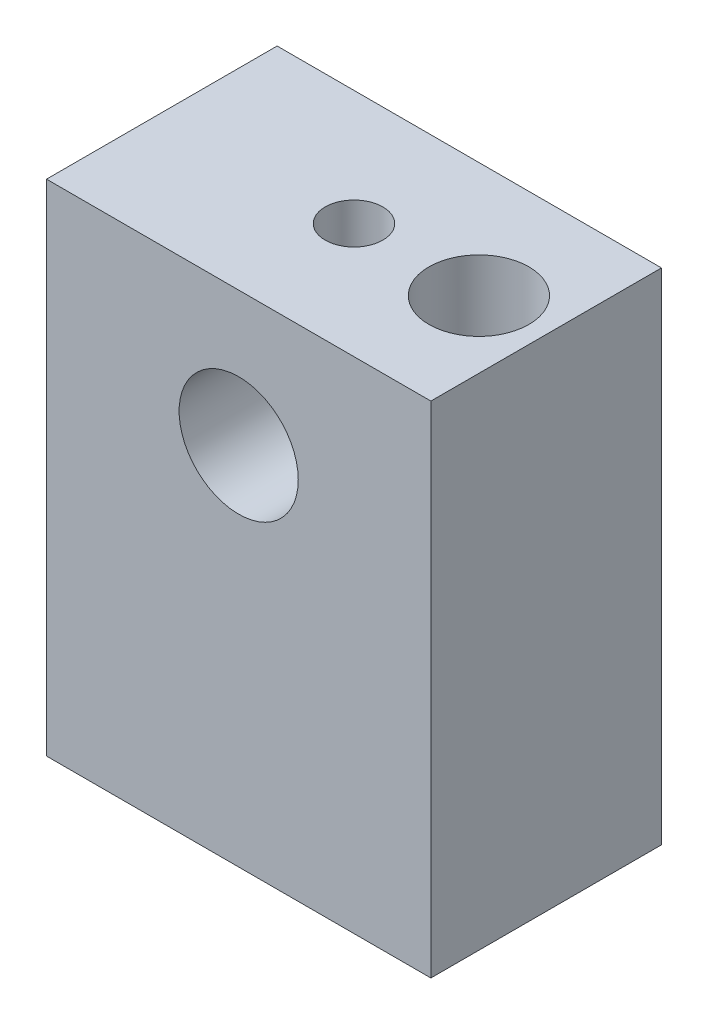
SolidWorks part; units mm, degrees
material "Brass"
ref_plane "Front Plane" through (0, 0, 0) normal (0, 0, 1) x (1, 0, 0)
ref_plane "Top Plane" through (0, 0, 0) normal (0, 1, 0) x (1, 0, 0)
ref_plane "Right Plane" through (0, 0, 0) normal (1, 0, 0) x (0, 0, -1)
sketch "Sketch1" plane through (0, 0, 0) normal (0, 0, 1) x (1, 0, 0)
  line L0 (-10, 0) -> (10, 0)
  line L1 (10, 0) -> (10, 26)
  line L2 (10, 26) -> (-10, 26)
  line L3 (-10, 26) -> (-10, 0)
extrude "Boss-Extrude1" add sketch "Sketch1" along normal blind 12
sketch "Sketch2" plane through (0, 0, 0) normal (0, 0, 1) x (1, 0, 0)
  circle A0 centre (0, 19) radius 3.1
  dimension "D1" = 6.2
extrude "Cut-Extrude1" cut sketch "Sketch2" against normal mid plane 80
sketch "Sketch3" plane through (0, 0, 0) normal (0, 1, 0) x (1, 0, 0)
  circle A0 centre (6.5, -6) radius 2.6
  circle A1 centre (0, -6) radius 1.5
  dimension "D1" = 5.2
  dimension "D2" = 3
extrude "Cut-Extrude2" cut sketch "Sketch3" against normal mid plane 80
